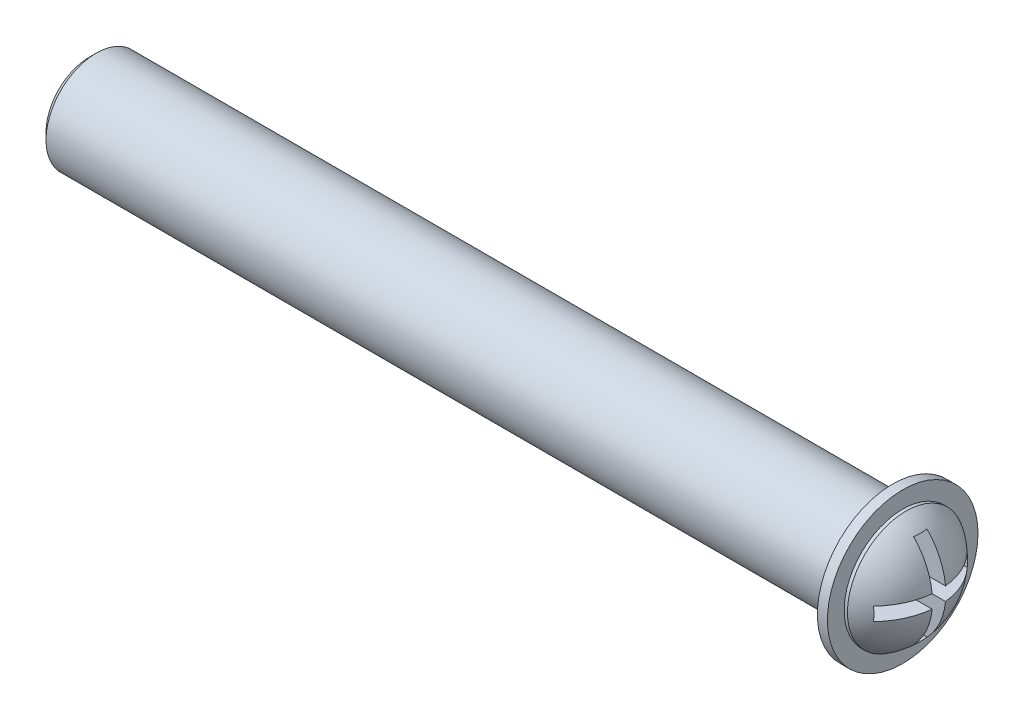
SolidWorks part; units mm, degrees
ref_plane "前视基准面" through (0, 0, 0) normal (0, 0, 1) x (1, 0, 0)
ref_plane "上视基准面" through (0, 0, 0) normal (0, 1, 0) x (1, 0, 0)
ref_plane "右视基准面" through (0, 0, 0) normal (1, 0, 0) x (0, 0, -1)
sketch "草图1" plane through (0, 0, 0) normal (1, 0, 0) x (0, 0, -1)
  circle A0 centre (0, 0) radius 2.25
  dimension "D1" = 4.5
extrude "凸台-拉伸1" add sketch "草图1" along normal blind 0.3
sketch "草图2" plane through (0, 0, 0) normal (-1, 0, 0) x (0, 0, 1)
  circle A0 centre (0, 0) radius 1.5
  dimension "D1" = 3
extrude "凸台-拉伸3" add sketch "草图2" along normal blind 24
sketch "草图5" plane through (0, 0, 0) normal (1, 0, 0) x (0, 0, -1)
  line L0 (0.2, 0.2) -> (1.4, 0.2)
  line L1 (1.4, 0.2) -> (1.4, -0.2)
  line L2 (1.4, -0.2) -> (0.2, -0.2)
  line L3 (0.2, -0.2) -> (0.2, -1.4)
  line L4 (0.2, -1.4) -> (-0.2, -1.4)
  line L5 (-0.2, -1.4) -> (-0.2, -0.2)
  line L6 (-0.2, -0.2) -> (-1.4, -0.2)
  line L7 (-1.4, -0.2) -> (-1.4, 0.2)
  line L8 (-1.4, 0.2) -> (-0.2, 0.2)
  line L9 (-0.2, 0.2) -> (-0.2, 1.4)
  line L10 (-0.2, 1.4) -> (0.2, 1.4)
  line L11 (0.2, 1.4) -> (0.2, 0.2)
  dimension "D1" = 0.4
  dimension "D2" = 0.4
  dimension "D3" = 0.4
  dimension "D4" = 0.4
  dimension "D5" = 0.2
  dimension "D6" = 0.2
  dimension "D7" = 0.2
  dimension "D8" = 0.2
  dimension "D9" = 1.2
  dimension "D10" = 1.2
  dimension "D11" = 1.2
  dimension "D12" = 1.2
sketch "草图6" plane through (0.3, 0, 0) normal (1, 0, 0) x (0, 0, -1)
  circle A0 centre (0, 0) radius 1.75
  dimension "D1" = 3.5
extrude "凸台-拉伸4" add sketch "草图6" along normal blind 0.1
dome "圆顶1" faces to dome 1 distance 1 reverse direction no elliptical dome no face at (0.4, 0, -1.75) parameters "D1"=1
extrude "切除-拉伸2" cut sketch "草图5" along normal blind 2
chamfer "倒角1" distance 0.2 angle 45 1 edges at (-24, 0, 1.5)
